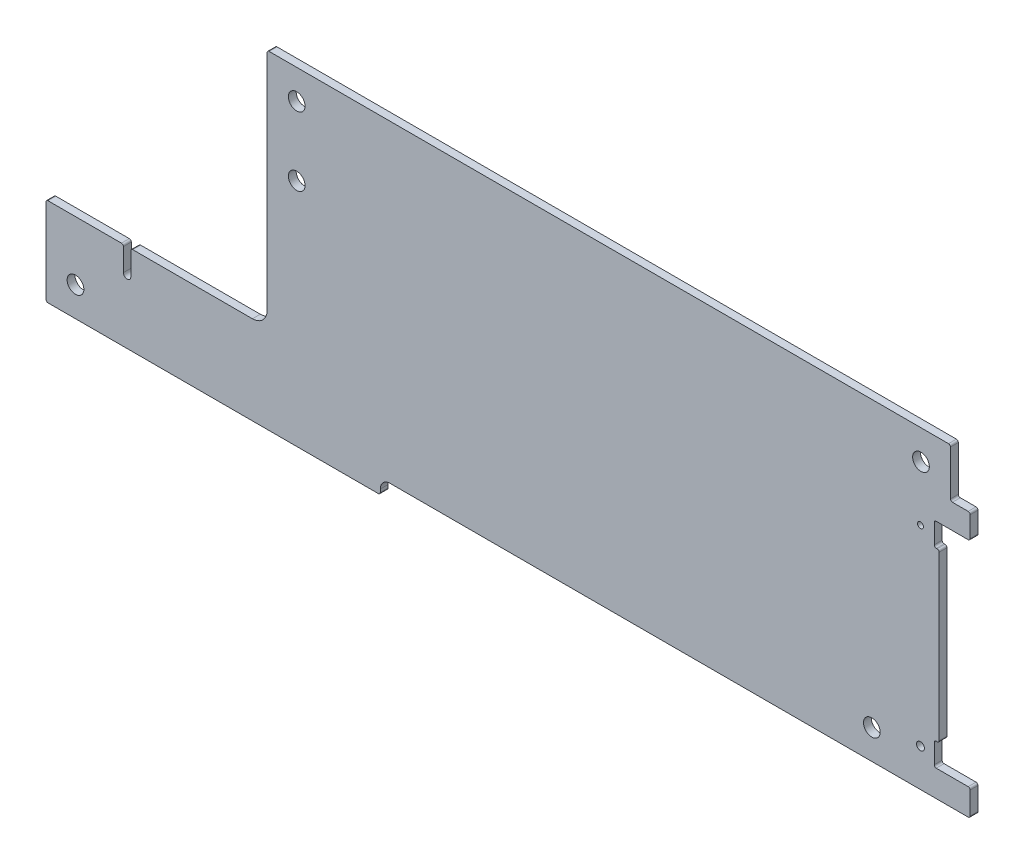
SolidWorks part; units mm, degrees
ref_plane "Front Plane" through (0, 0, 0) normal (0, 0, 1) x (1, 0, 0)
ref_plane "Top Plane" through (0, 0, 0) normal (0, 1, 0) x (1, 0, 0)
ref_plane "Right Plane" through (0, 0, 0) normal (1, 0, 0) x (0, 0, -1)
sketch "Sketch2" plane through (0, 0, 0) normal (0, 0, 1) x (1, 0, 0)
  line L0 (68, -2) -> (68, -3)
  line L1 (70, 0) -> (188, 0)
  line L2 (0, 0) -> (0, 15)
  line L3 (45, 63.8) -> (188, 63.8)
  line L4 (188, 0) -> (188, 63.8)
  line L11 (0, 15) -> (42, 15)
  line L12 (45, 63.8) -> (45, 18)
  line L13 (68, -3) -> (0, -3)
  line L14 (0, -3) -> (0, 0)
  arc A0 (42, 15) -> (45, 18) centre (42, 18) ccw
  arc A2 (68, -2) -> (70, 0) centre (70, -2) cw
  dimension "D7" = 3
  dimension "D8" = 2
  dimension "D1" = 63.8
  dimension "D2" = 188
  dimension "D3" = 15
  dimension "D4" = 45
  dimension "D5" = 3
  dimension "D6" = 120
extrude "Boss-Extrude1" add sketch "Sketch2" along normal blind 1.6
sketch "Sketch4" plane through (0, 0, 0) normal (0, 0, -1) x (-1, 0, 0)
  line L0 (-188, 49.271) -> (-188, 48.871)
  line L1 (-181.1, 48.871) -> (-187.6, 48.871)
  line L2 (-189.75, 27.121) -> (-173.65, 27.121) construction
  line L14 (-70, 0) -> (-188, 0) construction
  line L15 (-181.7, 43.721) -> (-181.7, 10.521)
  line L16 (-181.3, 10.121) -> (-181.1, 10.121)
  line L17 (-180.7, 9.721) -> (-180.7, 5.771)
  line L18 (-181.1, 5.371) -> (-187.6, 5.371)
  line L19 (-188, 0) -> (-188, 63.8) construction
  line L20 (-188, 5.371) -> (-188, 48.871)
  line L21 (-188, 4.971) -> (-188, 5.371)
  line L22 (-180.7, 44.521) -> (-180.7, 48.471)
  line L23 (-181.3, 44.121) -> (-181.1, 44.121)
  arc A9 (-180.7, 5.771) -> (-181.1, 5.371) centre (-181.1, 5.771) cw
  arc A10 (-181.7, 10.521) -> (-181.3, 10.121) centre (-181.3, 10.521) ccw
  arc A11 (-181.1, 10.121) -> (-180.7, 9.721) centre (-181.1, 9.721) cw
  arc A12 (-187.6, 5.371) -> (-188, 4.971) centre (-187.6, 4.971) ccw
  arc A13 (-187.6, 48.871) -> (-188, 49.271) centre (-187.6, 49.271) cw
  arc A14 (-181.1, 44.121) -> (-180.7, 44.521) centre (-181.1, 44.521) ccw
  arc A15 (-181.7, 43.721) -> (-181.3, 44.121) centre (-181.3, 43.721) cw
  arc A16 (-180.7, 48.471) -> (-181.1, 48.871) centre (-181.1, 48.471) ccw
  circle A17 centre (-177.9, 46.591) radius 0.6
  circle A18 centre (-177.9, 7.651) radius 0.8
  point P2 (-181.7, 44.121)
  point P11 (-181.7, 27.121)
  point P16 (-181.7, 10.121)
  point P23 (-182.15, 27.121)
  point P31 (-188, 27.121)
  point P37 (-188, 27.121)
  dimension "D1" = 27.121
  dimension "D12" = 19.47
  dimension "D13" = 19.47
  dimension "D6" = 0.4
  dimension "D7" = 0.4
  dimension "D10" = 1.6
  dimension "D11" = 1.2
  dimension "D2" = 17
  dimension "D3" = 6.3
  dimension "D4" = 43.5
  dimension "D5" = 7.3
  dimension "D8" = 10.1
  dimension "D9" = 10.1
extrude "Cut-Extrude1" cut sketch "Sketch4" against normal through all
sketch "Sketch5" plane through (0, 0, 1.6) normal (0, 0, 1) x (1, 0, 0)
  line L0 (42, 15) -> (0, 15) construction
  line L1 (15.75, 15) -> (17.25, 15)
  line L2 (15.75, 15) -> (15.75, 10)
  line L4 (17.25, 15) -> (17.25, 10)
  line L5 (0, 15) -> (0, -3) construction
  arc A0 (15.75, 10) -> (17.25, 10) centre (16.5, 10) ccw
  point P7 (16.5, 9.25)
  dimension "D1" = 1.5
  dimension "D2" = 5.75
  dimension "D3" = 16.5
extrude "Cut-Extrude2" cut sketch "Sketch5" against normal through all
sketch "Sketch6" plane through (0, 0, 1.6) normal (0, 0, 1) x (1, 0, 0)
  line L1 (188, 63.8) -> (184, 63.8)
  line L2 (188, 63.8) -> (188, 53.871)
  line L3 (187.6, 53.871) -> (184.4, 53.871)
  line L4 (184, 63.8) -> (184, 54.271)
  line L6 (181.1, 48.871) -> (187.6, 48.871) construction
  line L8 (188, 53.871) -> (188, 53.471)
  arc A0 (184.4, 53.871) -> (184, 54.271) centre (184.4, 54.271) cw
  arc A1 (187.6, 53.871) -> (188, 53.471) centre (187.6, 53.471) cw
  point P11 (0, 0)
  dimension "D3" = 0.4
  dimension "D4" = 0.4
  dimension "D1" = 5
  dimension "D2" = 4
extrude "Cut-Extrude3" cut sketch "Sketch6" against normal through all
fillet "Fillet1" radius 0.4 8 edges at (15.75, 15, 0.8) (17.25, 15, 0.8) (0, -3, 0.8) (68, -3, 0.8) (0, 15, 0.8) (45, 63.8, 0.8) (188, 0, 0.8) (184, 63.8, 0.8)
hole_wizard "M3 Clearance Hole1" positions "Sketch7" profile "Sketch8" hole size "M3" standard "ANSI Metric" end condition through all
sketch "Sketch7" plane through (0, 0, 0) normal (0, 0, -1) x (-1, 0, 0)
  line L0 (-188, 49.271) -> (-188, 53.471) construction
  line L1 (-183.6, 63.8) -> (-45.4, 63.8) construction
  line L2 (-45, 63.4) -> (-45, 18) construction
  line L3 (-70, 0) -> (-187.6, 0) construction
  line L4 (-188, 0.4) -> (-188, 4.971) construction
  line L5 (-0.4, -3) -> (-67.6, -3) construction
  line L6 (0, 14.6) -> (0, -2.6) construction
  point P0 (-178, 57.8)
  point P2 (-51, 57.8)
  point P4 (-6, 3)
  point P6 (-168, 6)
  point P23 (-51, 43.8)
  dimension "D1" = 10
  dimension "D2" = 6
  dimension "D3" = 6
  dimension "D4" = 6
  dimension "D5" = 6
  dimension "D6" = 20
  dimension "D7" = 6
  dimension "D8" = 6
  dimension "D9" = 20
  dimension "D10" = 6
sketch "Sketch8" plane through (178, 57.8, 0) normal (1, 0, 0) x (0, 1, 0)
  line L0 (0, 0) -> (0, 1.6)
  line L1 (0, 1.6) -> (1.7, 1.6)
  line L2 (1.7, 1.6) -> (1.7, 0)
  line L5 (1.7, 0) -> (0, 0)
  line L11 (0, -6.35) -> (0, 107.95) construction
  dimension "Thru Hole Dia." = 3.4
  dimension "Thru Hole Depth" = 1.6
ref_plane "Plane1" through (0, 0, 0.8) normal (0, 0, -1) x (-1, 0, 0)
